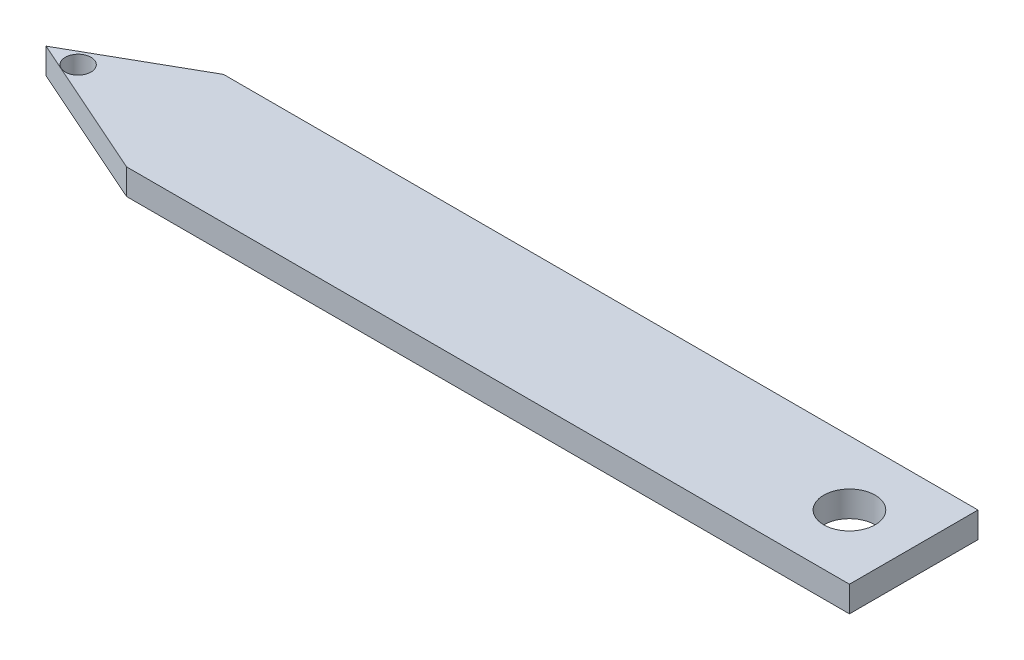
SolidWorks part; units mm, degrees
ref_plane "Front Plane" through (0, 0, 0) normal (0, 0, 1) x (1, 0, 0)
ref_plane "Top Plane" through (0, 0, 0) normal (0, 1, 0) x (1, 0, 0)
ref_plane "Right Plane" through (0, 0, 0) normal (1, 0, 0) x (0, 0, -1)
sketch "Sketch1" plane through (0, 0, 0) normal (0, 1, 0) x (1, 0, 0)
  line L1 (-26.205, 5.6294) -> (41.295, 5.6294)
  line L2 (-26.205, 5.6294) -> (-26.205, -4.3706)
  line L3 (-26.205, -4.3706) -> (41.295, -4.3706)
  line L4 (41.295, 5.6294) -> (41.295, -4.3706)
  circle A0 centre (-23.705, 0.6294) radius 1
  circle A1 centre (36.295, 0.6294) radius 2
  dimension "D3" = 2.5
  dimension "D1" = 10
  dimension "D2" = 67.5
  dimension "D4" = 5
extrude "Boss-Extrude1" add sketch "Sketch1" along normal blind 2
fillet "Fillet2" radius 5 1 edges at (-26.205, 1, -5.6294)
fillet "Fillet3" radius 5 1 edges at (-26.205, 1, 4.3706)
sketch "Sketch2" plane through (0, 2, 0) normal (0, 1, 0) x (1, 0, 0)
  line L0 (-26.205, 0.6294) -> (-17.3953, 5.6294)
  line L1 (41.295, 5.6294) -> (-21.205, 5.6294) construction
  line L2 (-17.3953, 5.6294) -> (-30.2763, 5.6294)
  line L3 (-30.2763, 5.6294) -> (-27.9574, -6.288)
  line L4 (-27.9574, -6.288) -> (-14.9325, -4.3706)
  line L5 (-21.205, -4.3706) -> (41.295, -4.3706) construction
  line L6 (-14.9325, -4.3706) -> (-26.205, 0.6294)
  arc A0 (-26.205, 0.6294) -> (-21.205, -4.3706) centre (-21.205, 0.6294) ccw construction
extrude "Cut-Extrude1" cut sketch "Sketch2" against normal blind 10
